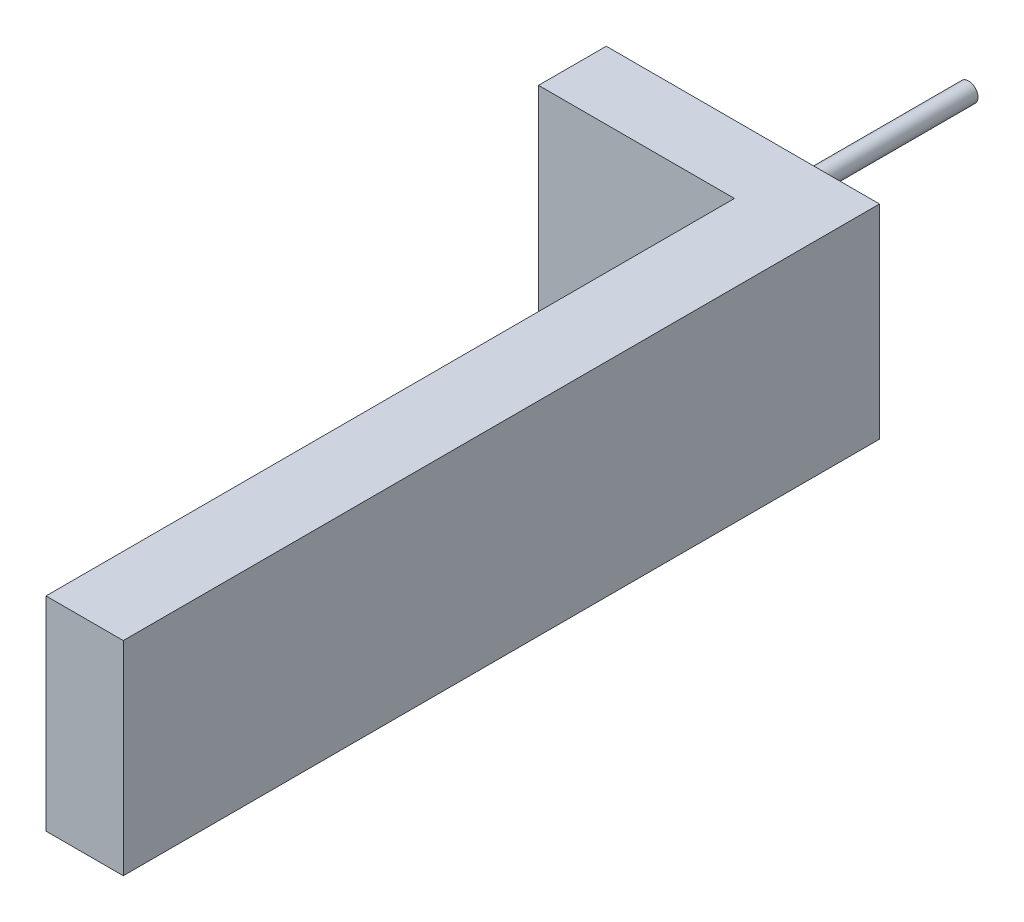
SolidWorks part; units mm, degrees
ref_plane "Front Plane" through (0, 0, 0) normal (0, 0, 1) x (1, 0, 0)
ref_plane "Top Plane" through (0, 0, 0) normal (0, 1, 0) x (1, 0, 0)
ref_plane "Right Plane" through (0, 0, 0) normal (1, 0, 0) x (0, 0, -1)
sketch "Sketch1" plane through (0, 0, 0) normal (0, 0, 1) x (1, 0, 0)
  circle A0 centre (0, 0) radius 1.39
extrude "Boss-Extrude1" add sketch "Sketch1" along normal blind 35.306
sketch "Sketch2" plane through (0, 0, 35.306) normal (0, 0, 1) x (1, 0, 0)
  line L1 (0, 0) -> (-18.1647, 0)
  line L2 (0, 0) -> (0, 14.4004)
  line L3 (0, 14.4004) -> (-18.1647, 14.4004)
  line L4 (-18.1647, 0) -> (-18.1647, 14.4004)
  line L5 (0, 0) -> (22.1564, 0)
  line L6 (0, 0) -> (0, 14.4004)
  line L7 (0, 14.4004) -> (22.1564, 14.4004)
  line L8 (22.1564, 0) -> (22.1564, 14.4004)
  line L9 (-18.1647, 0) -> (22.1564, 0)
  line L10 (-18.1647, 0) -> (-18.1647, -15.6636)
  line L11 (-18.1647, -15.6636) -> (22.1564, -15.6636)
  line L12 (22.1564, 0) -> (22.1564, -15.6636)
  circle M1 centre (0, 0) radius 1.39
extrude "Boss-Extrude2" add sketch "Sketch2" along normal blind 10 separate body contours L5 L8 L7 L2 M1 | L4 L1 L2 L3 M1 | L12 L5 L1 L10 L11 M1 region at (2.0055, -7.8668, 35.306) region at (-9.1319, 7.2388, 35.306) region at (11.1283, 7.2318, 35.306)
sketch "Sketch3" plane through (0, 0, 45.306) normal (0, 0, 1) x (1, 0, 0)
  line L0 (-18.1647, -15.6636) -> (22.1564, -15.6636) construction
  line L1 (22.1564, 14.4004) -> (10.7511, 14.4004)
  line L2 (22.1564, 14.4004) -> (22.1564, -15.6636)
  line L3 (22.1564, -15.6636) -> (10.7511, -15.6636)
  line L4 (10.7511, 14.4004) -> (10.7511, -15.6636)
extrude "Boss-Extrude3" add sketch "Sketch3" along normal blind 101.6
scale "Scale2" bodies to scale 103 101 scale about origin uniform scaling yes scale factor 10
